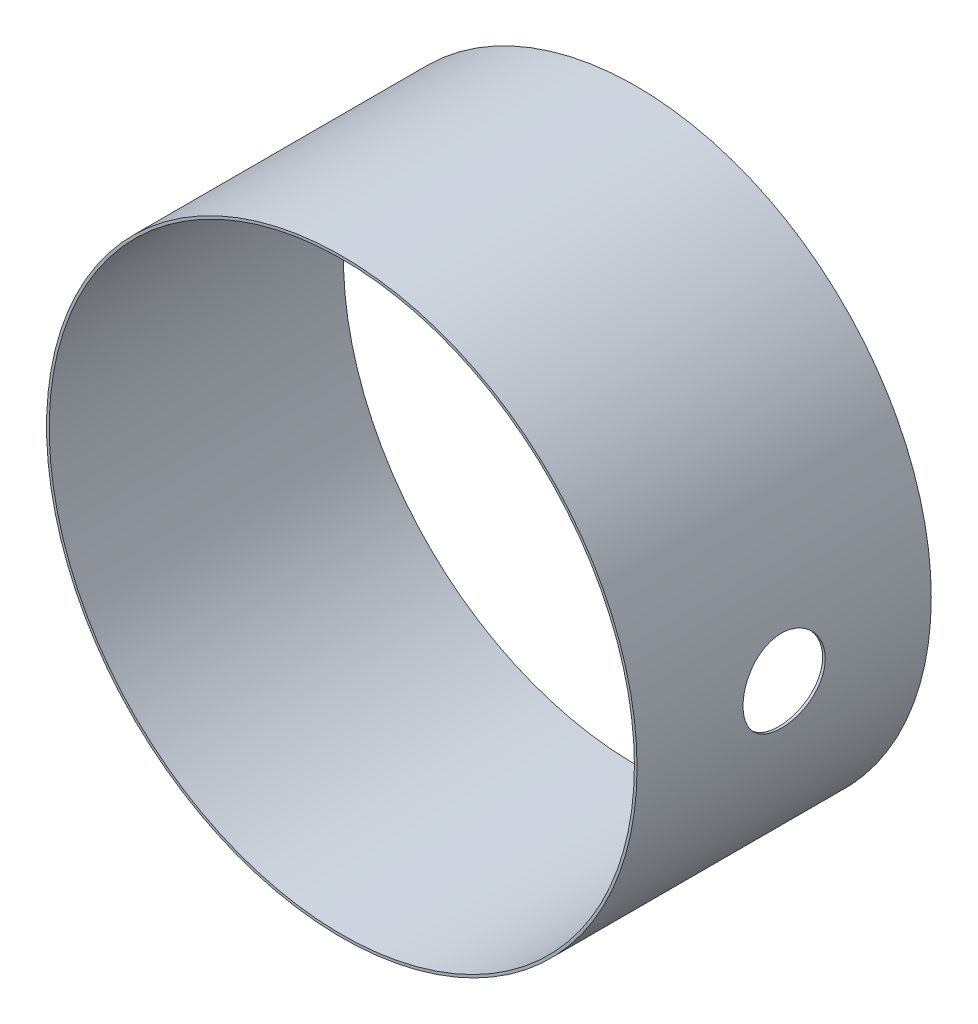
SolidWorks part; units mm, degrees
material "1023 Carbon Steel Sheet (SS)"
ref_plane "Front Plane" through (0, 0, 0) normal (0, 0, 1) x (1, 0, 0)
ref_plane "Top Plane" through (0, 0, 0) normal (0, 1, 0) x (1, 0, 0)
ref_plane "Right Plane" through (0, 0, 0) normal (1, 0, 0) x (0, 0, -1)
sketch "Sketch1" plane through (0, 0, 0) normal (0, 0, 1) x (1, 0, 0)
  circle B0 centre (0, 0) radius 1989
  circle B1 centre (0, 0) radius 2007
sketch_block_instance "Pressure vessel-1"
sketch_block "Pressure vessel" parameters "D1"=3978, "D2"=4291.7718
extrude "Boss-Extrude1" add sketch "Sketch1" along normal mid plane 2000
sketch "Sketch2" plane through (0, 0, 0) normal (1, 0, 0) x (0, 0, -1)
  circle A0 centre (0, 0) radius 279.5
  dimension "D1" = 559
extrude "Cut-Extrude1" cut sketch "Sketch2" along normal through all
